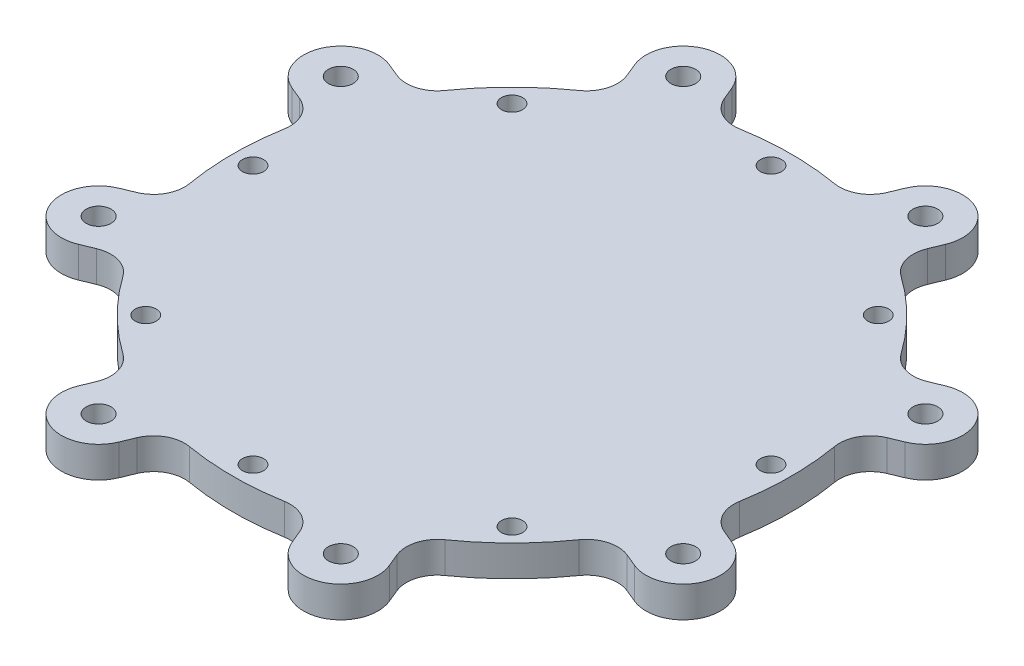
SolidWorks part; units mm, degrees
material "6061-T6 (SS)"
ref_plane "Front Plane" through (0, 0, 0) normal (0, 0, 1) x (1, 0, 0)
ref_plane "Top Plane" through (0, 0, 0) normal (0, 1, 0) x (1, 0, 0)
ref_plane "Right Plane" through (0, 0, 0) normal (1, 0, 0) x (0, 0, -1)
sketch "Sketch1" plane through (0, 0, 0) normal (0, 1, 0) x (1, 0, 0)
  circle A0 centre (0, 0) radius 45
  circle A1 centre (0, 41.75) radius 1.5
  circle A2 centre (29.5217, 29.5217) radius 1.5
  circle A3 centre (41.75, 0) radius 1.5
  circle A4 centre (29.5217, -29.5217) radius 1.5
  circle A5 centre (0, -41.75) radius 1.5
  circle A6 centre (-29.5217, -29.5217) radius 1.5
  circle A7 centre (-41.75, 0) radius 1.5
  circle A8 centre (-29.5217, 29.5217) radius 1.5
  point P22 (0, 0)
  dimension "D1" = 8
extrude "Boss-Extrude2" add sketch "Sketch1" along normal blind 5
sketch "Sketch9" plane through (0, 0, 0) normal (0, -1, 0) x (1, 0, 0)
  circle A2 centre (27, 0) radius 3.937
  circle A3 centre (0, -27) radius 3.937
  circle A4 centre (-27, 0) radius 3.937
  circle A5 centre (0, 27) radius 3.937
  point P15 (0, 0)
  dimension "D1" = 4
extrude "Boss-Extrude7" add sketch "Sketch9" along normal blind 4
sketch "Sketch10" plane through (0, 5, 0) normal (0, 1, 0) x (1, 0, 0)
  circle A0 centre (0, 41.75) radius 1.7
  circle A1 centre (29.5217, 29.5217) radius 1.7
  circle A2 centre (41.75, 0) radius 1.7
  circle A3 centre (29.5217, -29.5217) radius 1.7
  circle A4 centre (0, -41.75) radius 1.7
  circle A5 centre (-29.5217, -29.5217) radius 1.7
  circle A6 centre (-41.75, 0) radius 1.7
  circle A7 centre (-29.5217, 29.5217) radius 1.7
  point P19 (0, 0)
  dimension "D1" = 8
extrude "Cut-Extrude9" cut sketch "Sketch10" against normal blind 14
sketch "Sketch14" plane through (0, -4, 0) normal (0, -1, 0) x (1, 0, 0)
  point P0 (0, 27)
  point P1 (27, 0)
  point P3 (0, -27)
  point P5 (-27, 0)
hole_wizard "M3 Tapped Hole1" positions "Sketch14" profile "Sketch15" tap size "M3" standard "DIN"
sketch "Sketch15" plane through (0, -4, 27) normal (1, 0, 0) x (0, 0, -1)
  line L0 (0, 0) -> (0, 7.7511)
  line L1 (0, 7.7511) -> (1.25, 7)
  line L2 (1.25, 7) -> (1.25, 0)
  line L5 (1.25, 0) -> (0, 0)
  line L10 (0, 7.7511) -> (-1.25, 7) construction
  line L11 (0, -6.35) -> (0, 107.95) construction
  dimension "Tap Drill Dia." = 2.5
  dimension "Tap Drill Depth" = 7
  dimension "Drill Angle" = 118
cosmetic thread "Hole Thread1" parameters "D1"=10, "D2"=3
cosmetic thread "Hole Thread2" parameters "D1"=10, "D2"=3
cosmetic thread "Hole Thread3" parameters "D1"=10, "D2"=3
cosmetic thread "Hole Thread4" parameters "D1"=10, "D2"=3
sketch "Sketch17" plane through (0, 5, 0) normal (0, 1, 0) x (1, 0, 0)
  line L0 (0, 0) -> (41.5746, 17.2208)
  line L1 (41.5746, 17.2208) -> (47.1179, 19.5169)
  line L2 (47.1179, 19.5169) -> (44.8218, 25.0601)
  line L3 (47.1179, 19.5169) -> (44.8218, 25.0601)
  line L4 (44.8218, 25.0601) -> (49.414, 13.9736)
  line L5 (44.8218, 25.0601) -> (38.9073, 22.6103)
  line L6 (49.414, 13.9736) -> (43.4995, 11.5237)
  circle A0 centre (0, 0) radius 45
  circle A1 centre (47.1179, 19.5169) radius 6
  circle A2 centre (47.1179, 19.5169) radius 2
  circle M17 centre (0, 0) radius 45
extrude "Boss-Extrude10" add sketch "Sketch17" against normal up to surface (5 mm away) contours A2 L4 A1 | A2 L1 A1 L4 | A2 L4 A1 L1 | A1 L5 M17 | A1 L6 M17 region at (43.5135, 5, -21.0098) region at (44.4634, 5, -13.3897) region at (40.9083, 5, -21.9724) region at (45.6249, 5, -15.9125) region at (49.6665, 5, -20.5726) up to face at (0, 0, -40.05)
sketch "Sketch19" plane through (0, 5, 0) normal (0, 1, 0) x (1, 0, 0)
  circle A0 centre (0, 0) radius 3.3811
extrude "Boss-Extrude11" add sketch "Sketch19" along normal blind 10
fillet "Fillet1" radius 5 2 edges at (38.9073, 2.5, -22.6103) (43.4995, 2.5, -11.5237)
pattern_circular "CirPattern2" count 8 over 360 about axis through (0, 15, 0) along (0, 1, 0) of "Fillet1", "Boss-Extrude10"
sketch "Sketch20" plane through (0, 0, 0) normal (0, 0, 1) x (1, 0, 0)
  line L1 (-3.3811, 15) -> (3.3811, 15)
  line L2 (-3.3811, 15) -> (-3.3811, 5)
  line L3 (-3.3811, 5) -> (3.3811, 5)
  line L4 (3.3811, 15) -> (3.3811, 5)
extrude "Cut-Extrude10" cut sketch "Sketch20" against normal through all both and the other way through all
